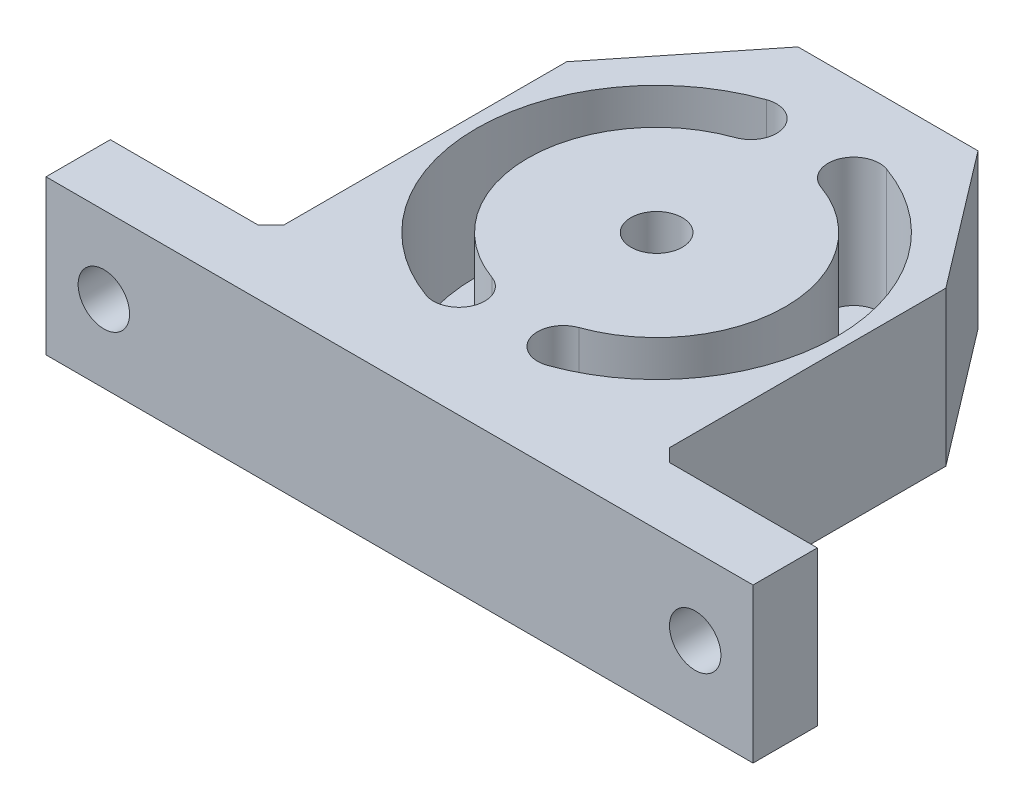
SolidWorks part; units mm, degrees
ref_plane "Front Plane" through (0, 0, 0) normal (0, 0, 1) x (1, 0, 0)
ref_plane "Top Plane" through (0, 0, 0) normal (0, 1, 0) x (1, 0, 0)
ref_plane "Right Plane" through (0, 0, 0) normal (1, 0, 0) x (0, 0, -1)
sketch "Sketch1" plane through (0, 0, 0) normal (0, 1, 0) x (1, 0, 0)
  line L0 (15, -16.5) -> (27.5, -16.5)
  line L1 (-27.5, -16.5) -> (-15, -16.5)
  line L2 (-27.5, -16.5) -> (-27.5, -21.5)
  line L3 (-27.5, -21.5) -> (27.5, -21.5)
  line L4 (27.5, -16.5) -> (27.5, -21.5)
  line L8 (-15, -16.5) -> (-15, 6.5)
  line L9 (-7, 16.5) -> (7, 16.5)
  line L10 (15, -16.5) -> (15, 6)
  line L12 (-15, 6.5) -> (-7, 16.5)
  line L13 (7, 16.5) -> (15, 6)
  point P0 (0, 0)
  point P5 (0, 0)
  point P15 (30.3078, 13.5018)
  dimension "D1" = 55
  dimension "D2" = 14
  dimension "D3" = 15
  dimension "D4" = 15
  dimension "D5" = 5
  dimension "D6" = 12.5
  dimension "D7" = 22.5
  dimension "D8" = 10.5
extrude "Boss-Extrude1" add sketch "Sketch1" along normal blind 12
sketch "Sketch2" plane through (0, 0, 21.5) normal (0, 0, 1) x (1, 0, 0)
  line L0 (-27.5, 12) -> (27.5, 12) construction
  line L1 (-27.5, 12) -> (-27.5, 0) construction
  circle A0 centre (-23, 6) radius 2
  circle A1 centre (23, 6) radius 2
  dimension "D1" = 6
  dimension "D2" = 4
  dimension "D3" = 46
  dimension "D4" = 4.5
extrude "Cut-Extrude1" cut sketch "Sketch2" against normal through all
sketch "Sketch3" plane through (0, 12, 0) normal (0, 1, 0) x (1, 0, 0)
  line L0 (-27.5, -21.5) -> (27.5, -21.5) construction
  line L1 (0, -1.5) -> (0, 10.5)
  line L2 (15, -16.5) -> (15, 6) construction
  circle A3 centre (0, -1.5) radius 2
  arc A7 (-4.0061, 9.8311) -> (-4.0549, -12.8137) centre (0, -1.5) ccw construction
  arc A8 (-4.0061, 9.8311) -> (-4.0549, -12.8137) centre (0, -1.5) ccw construction
  arc A9 (-4.6728, 11.7167) -> (-4.7297, -14.6964) centre (0, -1.5) ccw
  arc A10 (-3.3395, 7.9455) -> (-3.3801, -10.931) centre (0, -1.5) ccw
  arc A11 (-3.3395, 7.9455) -> (-4.6728, 11.7167) centre (-4.0061, 9.8311) ccw
  arc A12 (-4.7297, -14.6964) -> (-3.3801, -10.931) centre (-4.0549, -12.8137) ccw
  arc A13 (4.0061, 9.8311) -> (4.0549, -12.8137) centre (0, -1.5) cw construction
  arc A14 (4.6728, 11.7167) -> (4.7297, -14.6964) centre (0, -1.5) cw
  arc A15 (3.3395, 7.9455) -> (3.3801, -10.931) centre (0, -1.5) cw
  arc A16 (3.3395, 7.9455) -> (4.6728, 11.7167) centre (4.0061, 9.8311) cw
  arc A17 (4.7297, -14.6964) -> (3.3801, -10.931) centre (4.0549, -12.8137) cw
  point P5 (-12.0184, -1.4741)
  point P17 (12.0184, -1.4741)
  dimension "D1" = 20
  dimension "D3" = 2
  dimension "D2" = 15
extrude "Cut-Extrude2" cut sketch "Sketch3" against normal blind 10 contours A9 A12 A10 A11 | A17 A14 A16 A15 region at (-2.3961, 12, -10.4003) region at (13.7261, 12, 1.4704)
extrude "Cut-Extrude3" cut sketch "Sketch3<7>" against normal through all contours A3 region at (-1.3742, 12, 2.8742)
sketch "Sketch3<7>" plane through (0, 12, 0) normal (0, 1, 0) x (1, 0, 0) same geometry as "Sketch3"
chamfer "Chamfer1" distance 1 angle 45 2 edges at (-15, 6, 16.5) (15, 6, 16.5)
